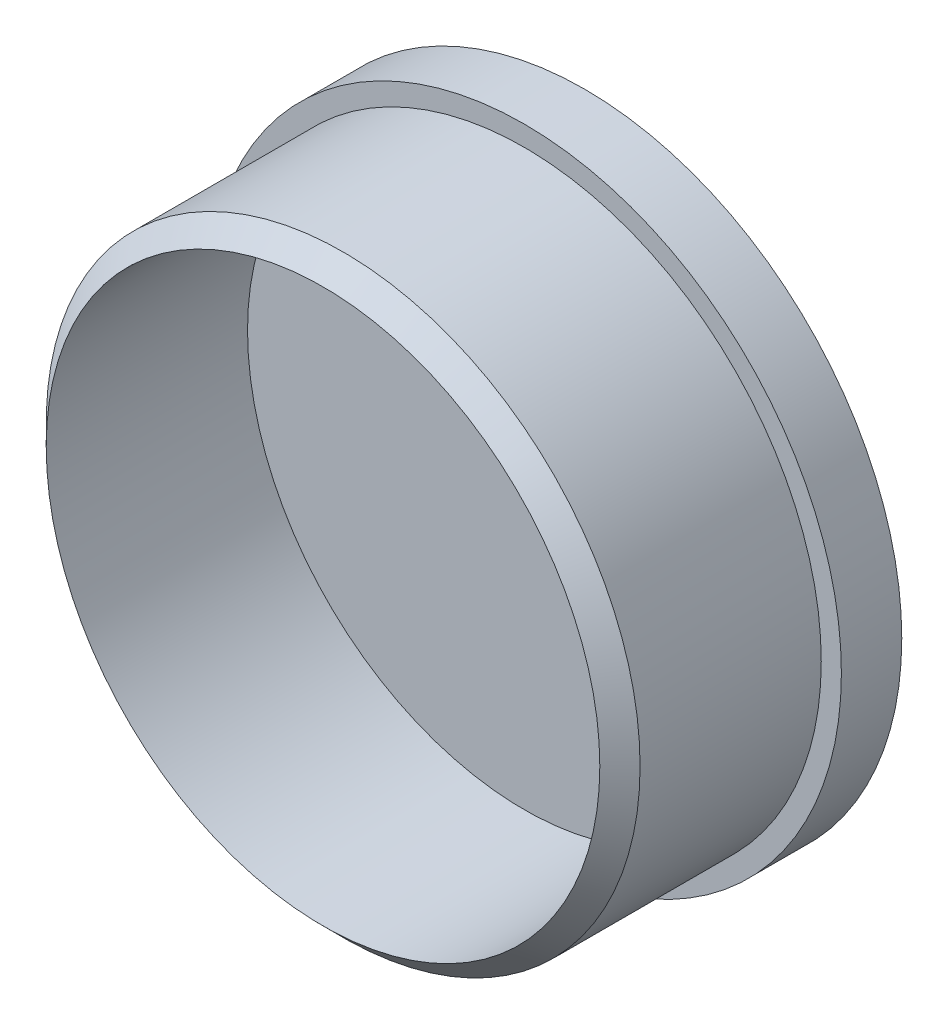
SolidWorks part; units mm, degrees
material "Plástico personalizado (1)"
ref_plane "Plano frontal" through (0, 0, 0) normal (0, 0, 1) x (1, 0, 0)
ref_plane "Plano superior" through (0, 0, 0) normal (0, 1, 0) x (1, 0, 0)
ref_plane "Plano direito" through (0, 0, 0) normal (1, 0, 0) x (0, 0, -1)
sketch "Esboço1" plane through (0, 0, 0) normal (0, 0, 1) x (1, 0, 0)
  circle A0 centre (0, 0) radius 31.5
extrude "Ressalto-extrusão1" add sketch "Esboço1" along normal blind 6
sketch "Esboço2" plane through (0, 0, 6) normal (0, 0, 1) x (1, 0, 0)
  circle A0 centre (0, 0) radius 29.5
  circle A1 centre (0, 0) radius 27.5
  dimension "D1" = 59
extrude "Ressalto-extrusão2" add sketch "Esboço2" along normal blind 20
chamfer "Chanfro1" distance 2 angle 45 1 edges at (29.5, 0, 26)
